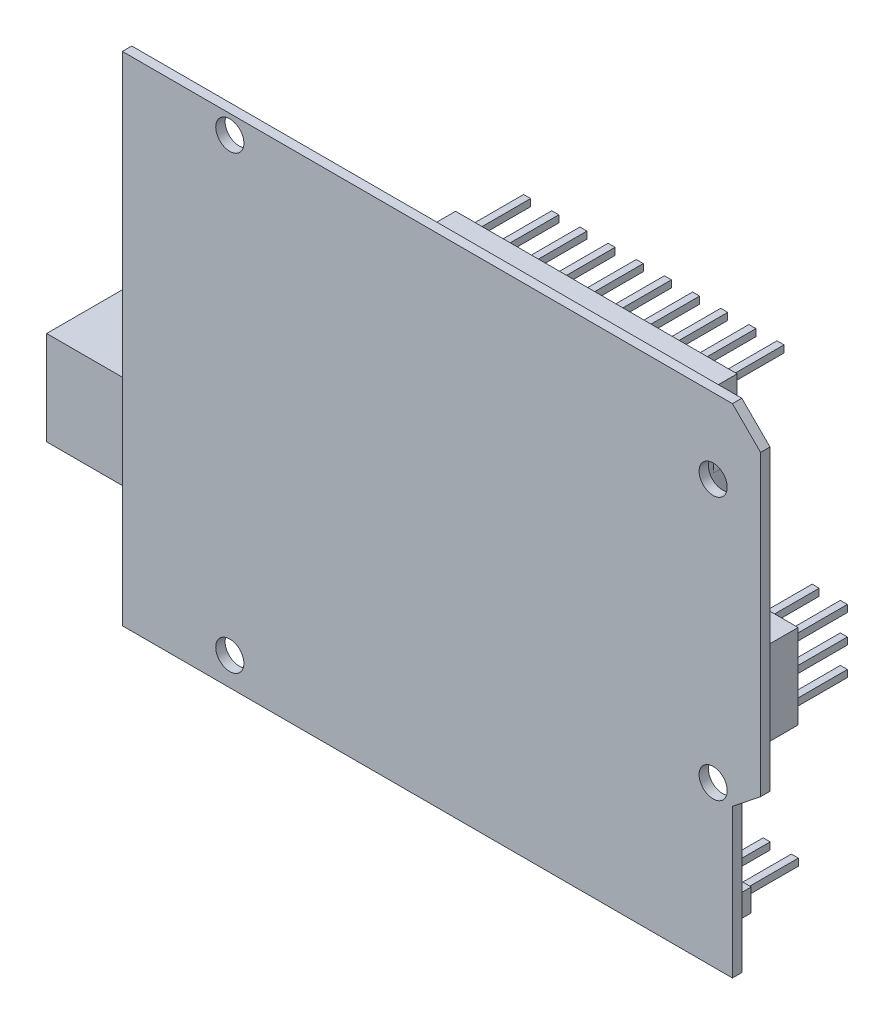
SolidWorks part; units mm, degrees
ref_plane "Front Plane" through (0, 0, 0) normal (0, 0, 1) x (1, 0, 0)
ref_plane "Top Plane" through (0, 0, 0) normal (0, 1, 0) x (1, 0, 0)
ref_plane "Right Plane" through (0, 0, 0) normal (1, 0, 0) x (0, 0, -1)
sketch "Sketch1" plane through (0, 0, 0) normal (0, 0, 1) x (1, 0, 0)
  line L0 (22.754, 124.2709) -> (19.754, 127.2709)
  line L1 (19.754, 74.2709) -> (-45.246, 74.2709)
  line L2 (22.754, 92.5002) -> (22.754, 124.2709)
  line L3 (19.754, 127.2709) -> (-45.246, 127.2709)
  line L4 (-45.246, 74.2709) -> (-45.246, 127.2709)
  line L5 (22.754, 92.5002) -> (19.754, 90.1139)
  line L6 (19.754, 90.1139) -> (19.754, 74.2709)
extrude "Boss-Extrude1" add sketch "Sketch1" against normal blind 1
sketch "Sketch2" plane through (0, 0, -1) normal (0, 0, -1) x (-1, 0, 0)
  line L1 (38.3165, 86.2081) -> (54.3165, 86.2081)
  line L2 (38.3165, 86.2081) -> (38.3165, 96.2081)
  line L3 (38.3165, 96.2081) -> (54.3165, 96.2081)
  line L4 (54.3165, 86.2081) -> (54.3165, 96.2081)
  dimension "D1" = 16
  dimension "D2" = 10
extrude "Boss-Extrude2" add sketch "Sketch2" along normal blind 10
sketch "Sketch3" plane through (-54.3165, 0, 0) normal (-1, 0, 0) x (0, 0, 1)
  line L1 (-8.51, 88.5529) -> (-3.6209, 88.5529)
  line L2 (-8.51, 88.5529) -> (-8.51, 93.9309)
  line L3 (-8.51, 93.9309) -> (-3.6209, 93.9309)
  line L4 (-3.6209, 88.5529) -> (-3.6209, 93.9309)
extrude "Cut-Extrude1" cut sketch "Sketch3" against normal blind 10
sketch "Sketch4" plane through (0, 0, -1) normal (0, 0, -1) x (-1, 0, 0)
  line L0 (45.246, 74.2709) -> (-19.754, 74.2709) construction
  line L1 (-16.754, 76.2709) -> (28.246, 76.2709)
  line L2 (-16.754, 76.2709) -> (-16.754, 78.6709)
  line L3 (-16.754, 78.6709) -> (28.246, 78.6709)
  line L4 (28.246, 76.2709) -> (28.246, 78.6709)
  line L5 (-15.254, 125.2709) -> (14.746, 125.2709)
  line L6 (-15.254, 125.2709) -> (-15.254, 122.8709)
  line L7 (-15.254, 122.8709) -> (14.746, 122.8709)
  line L8 (14.746, 125.2709) -> (14.746, 122.8709)
  line L9 (-19.754, 127.2709) -> (45.246, 127.2709) construction
  line L10 (-22.754, 92.5002) -> (-22.754, 124.2709) construction
  line L11 (-19.754, 74.2709) -> (-19.754, 90.1139) construction
  dimension "D1" = 2.4
  dimension "D2" = 2.4
  dimension "D3" = 2
  dimension "D4" = 2
  dimension "D5" = 7.5
  dimension "D6" = 3
  dimension "D7" = 45
  dimension "D8" = 30
extrude "Boss-Extrude3" add sketch "Sketch4" along normal blind 4
sketch "Sketch5" plane through (0, 0, -1) normal (0, 0, -1) x (-1, 0, 0)
  line L0 (-15.254, 122.8709) -> (14.746, 122.8709) construction
  line L1 (-13.754, 118.3709) -> (21.246, 118.3709)
  line L2 (-13.754, 118.3709) -> (-13.754, 108.3709)
  line L3 (-13.754, 108.3709) -> (21.246, 108.3709)
  line L4 (21.246, 118.3709) -> (21.246, 108.3709)
  line L5 (-22.754, 92.5002) -> (-22.754, 124.2709) construction
  dimension "D1" = 10
  dimension "D2" = 35
  dimension "D3" = 4.5
  dimension "D4" = 9
extrude "Boss-Extrude4" add sketch "Sketch5" along normal blind 7
sketch "Sketch6" plane through (0, 0, -8) normal (0, 0, -1) x (-1, 0, 0)
  line L0 (21.246, 108.3709) -> (21.246, 118.3709) construction
  line L1 (-13.754, 118.3709) -> (21.246, 118.3709)
  line L2 (-13.754, 118.3709) -> (-13.754, 116.8709)
  line L3 (-13.754, 116.8709) -> (21.246, 116.8709)
  line L4 (21.246, 118.3709) -> (21.246, 116.8709)
  line L6 (-13.754, 108.3709) -> (21.246, 108.3709)
  line L7 (-13.754, 108.3709) -> (-13.754, 109.8709)
  line L8 (-13.754, 109.8709) -> (21.246, 109.8709)
  line L9 (21.246, 108.3709) -> (21.246, 109.8709)
  dimension "D1" = 1.5
  dimension "D2" = 1.5
extrude "Cut-Extrude2" cut sketch "Sketch6" against normal blind 4
fillet "Fillet1" radius 1 4 edges at (-21.246, 116.8709, -6) (-21.246, 109.8709, -6) (13.754, 116.8709, -6) (13.754, 109.8709, -6)
sketch "Sketch7" plane through (0, 0, -1) normal (0, 0, -1) x (-1, 0, 0)
  circle A0 centre (-17.7001, 119.2709) radius 1.5
  circle A1 centre (-17.7001, 91.2709) radius 1.5
  circle A2 centre (33.7999, 125.2709) radius 1.5
  circle A3 centre (33.7999, 77.2709) radius 1.5
  point P10 (0, 0)
  point P11 (0, 0)
extrude "Cut-Extrude3" cut sketch "Sketch7" against normal blind 4
sketch "Sketch8" plane through (0, 0, -5) normal (0, 0, -1) x (-1, 0, 0)
  line L0 (-15.254, 124.0709) -> (14.746, 124.0709) construction
  line L1 (-14.254, 124.4459) -> (-13.504, 124.4459)
  line L2 (-14.254, 124.4459) -> (-14.254, 123.6959)
  line L3 (-14.254, 123.6959) -> (-13.504, 123.6959)
  line L4 (-13.504, 124.4459) -> (-13.504, 123.6959)
  line L5 (-15.254, 125.2709) -> (-15.254, 122.8709) construction
  line L6 (14.746, 122.8709) -> (14.746, 125.2709) construction
  dimension "D1" = 0.75
  dimension "D2" = 0.75
  dimension "D3" = 0.375
  dimension "D4" = 1
extrude "Boss-Extrude5" add sketch "Sketch8" along normal blind 6
pattern_linear "LPattern1" count 10 spacing 3 along (-1, 0, 0) of "Boss-Extrude5"
sketch "Sketch9" plane through (0, 0, -5) normal (0, 0, -1) x (-1, 0, 0)
  line L0 (-16.754, 77.4709) -> (28.246, 77.4709) construction
  line L1 (-16.754, 78.6709) -> (-16.754, 76.2709) construction
  line L2 (28.246, 76.2709) -> (28.246, 78.6709) construction
  line L4 (-15.7778, 77.8459) -> (-15.0278, 77.8459)
  line L5 (-15.7778, 77.8459) -> (-15.7778, 77.0959)
  line L6 (-15.7778, 77.0959) -> (-15.0278, 77.0959)
  line L7 (-15.0278, 77.8459) -> (-15.0278, 77.0959)
  dimension "D1" = 0.75
  dimension "D2" = 0.75
  dimension "D3" = 0.375
extrude "Boss-Extrude6" add sketch "Sketch9" along normal blind 6
pattern_linear "LPattern2" count 15 spacing 3 along (-1, 0, 0) of "Boss-Extrude6"
sketch "Sketch10" plane through (0, 0, -1) normal (0, 0, -1) x (-1, 0, 0)
  circle A0 centre (26.5467, 118.215) radius 2.5
  circle A1 centre (31.9407, 118.215) radius 2.5
  dimension "D1" = 5
  dimension "D2" = 5
extrude "Boss-Extrude7" add sketch "Sketch10" along normal blind 6
sketch "Sketch11" plane through (0, 0, -1) normal (0, 0, -1) x (-1, 0, 0)
  line L1 (-21.7492, 96.1139) -> (-16.9492, 96.1139)
  line L2 (-21.7492, 96.1139) -> (-21.7492, 105.1139)
  line L3 (-21.7492, 105.1139) -> (-16.9492, 105.1139)
  line L4 (-16.9492, 96.1139) -> (-16.9492, 105.1139)
  dimension "D1" = 4.8
  dimension "D2" = 9
  dimension "D3" = 6
extrude "Boss-Extrude8" add sketch "Sketch11" along normal up to surface (4 mm away) up to face at (0.254, 124.0709, -5)
sketch "Sketch12" plane through (0, 0, -5) normal (0, 0, -1) x (-1, 0, 0)
  line L0 (-21.7492, 96.1139) -> (-16.9492, 96.1139) construction
  line L1 (-20.9992, 97.8639) -> (-20.2492, 97.8639)
  line L2 (-20.9992, 97.8639) -> (-20.9992, 97.1139)
  line L3 (-20.9992, 97.1139) -> (-20.2492, 97.1139)
  line L4 (-20.2492, 97.8639) -> (-20.2492, 97.1139)
  line L5 (-21.7492, 105.1139) -> (-21.7492, 96.1139) construction
  dimension "D1" = 0.75
  dimension "D2" = 0.75
  dimension "D3" = 1
  dimension "D4" = 0.75
extrude "Boss-Extrude9" add sketch "Sketch12" along normal blind 6
pattern_linear "LPattern3" count 3 spacing 3 along (0, 1, 0) count 2 spacing 3 along (-1, 0, 0) of "Boss-Extrude9"
sketch "Sketch13" plane through (0, 0, -1) normal (0, 0, -1) x (-1, 0, 0)
  line L1 (16.3872, 103.9285) -> (30.5081, 103.9285)
  line L2 (16.3872, 103.9285) -> (16.3872, 99.5659)
  line L3 (16.3872, 99.5659) -> (30.5081, 99.5659)
  line L4 (30.5081, 103.9285) -> (30.5081, 99.5659)
extrude "Boss-Extrude10" add sketch "Sketch13" along normal blind 4
fillet "Fillet2" radius 1 4 edges at (-30.5081, 103.9285, -3) (-30.5081, 99.5659, -3) (-16.3872, 103.9285, -3) (-16.3872, 99.5659, -3)
